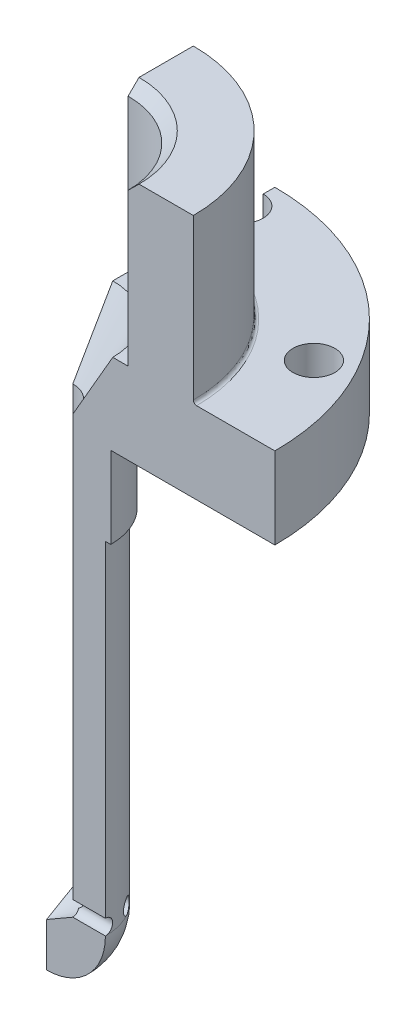
SolidWorks part; units mm, degrees
note: '?' marks a value the reader was unsure of.
ref_plane "Front Plane" through (0, 0, 0) normal (0, 0, 1) x (1, 0, 0)
ref_plane "Top Plane" through (0, 0, 0) normal (0, 1, 0) x (1, 0, 0)
ref_plane "Right Plane" through (0, 0, 0) normal (1, 0, 0) x (0, 0, -1)
sketch "Sketch1" plane through (0, 0, 0) normal (0, 0, 1) x (1, 0, 0)
  line L0 (-4.5847, -3.5328) -> (-2.0447, -3.5328)
  line L1 (0, 8.2157) -> (0, -2.0672) construction
  line L2 (-4.5847, 23.0788) -> (-2.0447, 23.0788)
  line L3 (-4.5847, -3.5328) -> (-4.5847, 23.0788)
  line L7 (-2.0447, 23.0788) -> (-2.0447, -3.5328)
  dimension "D2" = 4.5847
  dimension "D3" = 2.0447
  dimension "D4" = 26.6116
revolve "Revolve2" add sketch "Sketch1" angle 360 about L1
ref_plane "Plane1" through (-4.5847, 0, 0) normal (-1, 0, 0) x (0, 0, 1)
ref_axis "Axis2" through (0, -3.5328, 0) along (0, 1, 0)?
ref_plane "Plane2" through (0, 23.0788, 0) normal (0, -1, 0) x (-1, 0, 0)
sketch "Sketch3" plane through (0, 23.0788, 0) normal (0, -1, 0) x (-1, 0, 0)
  circle A0 centre (0, 0) radius 2.0447 construction
  circle A1 centre (0, 0) radius 4.5847 construction
  circle A2 centre (0, 0) radius 2.0447
  circle A3 centre (0, 0) radius 4.5847
extrude "Boss-Extrude1" add sketch "Sketch3" against normal blind 6.35
ref_plane "Plane3" through (0, 29.4288, 0) normal (0, 1, 0) x (1, 0, 0)
sketch "Sketch4" plane through (0, 29.4288, 0) normal (0, 1, 0) x (1, 0, 0)
  circle A0 centre (0, 0) radius 17.78
  circle A1 centre (0, 0) radius 2.0447
  dimension "D2" = 17.78
  dimension "D1" = 4.0894
extrude "Boss-Extrude2" add sketch "Sketch4" along normal blind 6.35
sketch "Sketch11" plane through (0, 35.7788, 0) normal (0, 1, 0) x (1, 0, 0)
  line L0 (0, 0) -> (0, -15.24) construction
  circle A0 centre (0, -15.24) radius 1.6319
  circle A1 centre (0, 0) radius 15.24 construction
  dimension "D2" = 3.2639
extrude "Cut-Extrude2" cut sketch "Sketch11" against normal up to next
ref_axis "Axis1" through (0, -3.5328, 0) along (0, 1, 0)?
pattern_circular "CirPattern2" count 6 over 360 about axis through (0, 0, 0) along (0, 1, 0) of "Cut-Extrude2"
chamfer "Chamfer1" distance 3.1128 angle 60 1 edges at (0, 35.7788, 2.0447)
sketch "Sketch13" plane through (0, 35.7788, 0) normal (0, 1, 0) x (1, 0, 0)
  circle A0 centre (0, 0) radius 6.35
  circle A1 centre (0, 0) radius 11.43
extrude "Boss-Extrude4" add sketch "Sketch13" along normal blind 12.7
fillet "Fillet4" radius 0.254 1 edges at (0, 35.7788, 11.43)
chamfer "Chamfer2" distance 0.8517 distance2 0.8395 1 edges at (0, 48.4788, 6.35)
sketch "Sketch14" plane through (0, 35.7788, 0) normal (0, 1, 0) x (1, 0, 0)
  circle A0 centre (-13.1982, -7.62) radius 2.794
sketch "Sketch15" plane through (0, 29.4288, 0) normal (0, -1, 0) x (1, 0, 0)
  circle A0 centre (0, 0) radius 5
  circle A1 centre (0, 0) radius 3.556
extrude "Boss-Extrude5" add sketch "Sketch15" along normal blind 6.35
sketch "Sketch18" plane through (0, -3.5328, 0) normal (0, -1, 0) x (1, 0, 0)
  circle A0 centre (0, 0) radius 4.318
sketch "Sketch19" plane through (0, 0, 0) normal (0, 0, 1) x (1, 0, 0)
  line L0 (0, -3.5328) -> (-4.5847, -3.5328)
  line L1 (-4.318, -3.5328) -> (4.318, -3.5328) construction
  line L2 (0, -3.5328) -> (0, -8.1175)
  arc A0 (-4.5847, -3.5328) -> (0, -8.1175) centre (0, -3.5328) ccw
  dimension "D2" = 4.5847
  dimension "D1" = 4.5847
ref_axis "Axis3" through (0, -3.5328, 0) along (0, -1, 0)
revolve "Revolve4" add sketch "Sketch19" angle 360 about axis through (0, -3.5328, 0) along (0, -1, 0)
sketch "Sketch20" plane through (-4.5847, 0, 0) normal (-1, 0, 0) x (0, 0, 1)
  line L1 (0, -3.5328) -> (0, -8.1175) construction
  line L2 (-4.318, -3.5328) -> (4.318, -3.5328) construction
  circle A0 centre (0, -2.9372) radius 0.5956
  dimension "D2" = 1.1913
extrude "Cut-Extrude3" cut sketch "Sketch20" against normal up to next
pattern_circular "CirPattern3" count 12 over 360 about axis through (0, -3.5328, 0) along (0, -1, 0) of "Cut-Extrude3"
sketch "Sketch21" plane through (0, 0, 0) normal (0, 0, 1) x (1, 0, 0)
  line L0 (0, -3.5328) -> (0, -4.7133)
  line L1 (-4.318, -3.5328) -> (4.318, -3.5328) construction
  line L5 (0, -3.5328) -> (-2.0447, -3.5328)
  line L6 (-2.0447, -3.5328) -> (0, -4.7133)
  spline S0 degree 2 poles (-1.975, -3.2105) (-1.9969, -3.3689) (-2.0447, -3.5328) knots 0.670969 0.670969 0.670969 1 1 1 weights 0.002248 0.002444 0.00264 construction
  dimension "D1" = 30
revolve "Cut-Revolve4" cut sketch "Sketch21" angle 360 about axis through (0, -3.5328, 0) along (0, -1, 0)
sketch "Sketch22" plane through (0, 48.4788, 0) normal (0, 1, 0) x (1, 0, 0)
  line L0 (0, 0) -> (0, 19.8928)
  line L1 (0, 19.8928) -> (-23.5228, 19.8928)
  line L2 (-23.5228, 19.8928) -> (-23.5228, -23.8862)
  line L3 (-23.5228, -23.8862) -> (22.702, -23.8862)
  line L4 (22.702, -23.8862) -> (22.702, 0)
  line L5 (22.702, 0) -> (0, 0)
extrude "Cut-Extrude4" cut sketch "Sketch22" against normal through all
equation "\"ManifoldThickness\"= 0.25"
equation "\"D1@Boss-Extrude1\"=\"ManifoldThickness\""
equation "\"SkipDistance\"= \"OD\"'equal to pintle OD"
equation "\"OD\"= \"ID\" + 2 * 0.1'Inner diameter plus wall thickness"
equation "\"AnnulusLength\"= 0.3084"
equation "\"ManifoldChamberThickness\"= 0.3314"
equation "\"D4@Sketch1\"=\"SkipDistance\"+\"AnnulusLength\"+\"ManifoldChamberThickness\"+\"HoleHeight\""
equation "\"HoleHeight\"= 0.0469"
equation "\"D2@Sketch1\"=\"OD\"/2"
equation "\"IR\"= 0.1610 / 2"
equation "\"D3@Sketch1\" = \"IR\""
equation "\"ID\"= \"IR\" * 2"
equation "\"440loose\"= 0.1285"
equation "\"D2@Sketch11\"=\"440loose\""
equation "\"ManifoldPlateThickness\"= 0.25"
equation "\"WeldHeight\"= 0.035"
equation "\"HoleFromEnd\"= \"HoleHeight\" / 2"
equation "\"D1@Sketch20\"=\"HoleFromEnd\""
equation "\"D2@Sketch20\"=\"HoleHeight\""
equation "\"D1@Sketch19\"=\"OD\"/2"
equation "\"D1@Sketch4\"=\"ID\""
